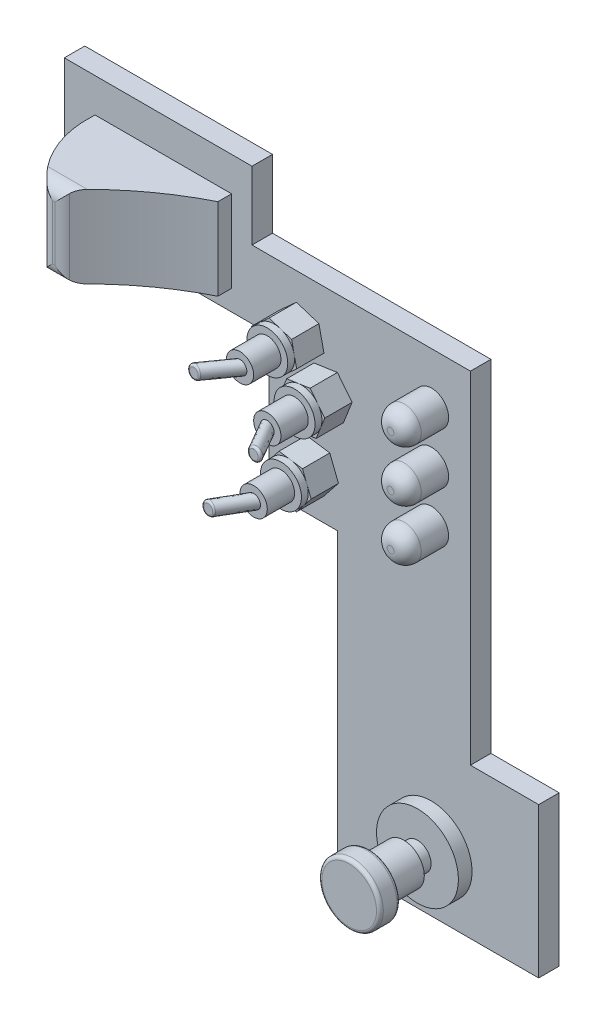
SolidWorks part; units mm, degrees
ref_plane "Front Plane" through (0, 0, 0) normal (0, 0, 1) x (1, 0, 0)
ref_plane "Top Plane" through (0, 0, 0) normal (0, 1, 0) x (1, 0, 0)
ref_plane "Right Plane" through (0, 0, 0) normal (1, 0, 0) x (0, 0, -1)
sketch "Sketch1" plane through (0, 0, 0) normal (0, 0, 1) x (1, 0, 0)
  line L1 (0, 0) -> (76.5, 0)
  line L2 (0, 0) -> (0, 100)
  line L3 (0, 100) -> (76.5, 100)
  line L4 (76.5, 0) -> (76.5, 100)
  dimension "D1" = 100
  dimension "D2" = 76.5
extrude "Boss-Extrude1" add sketch "Sketch1" along normal blind 3
sketch "Sketch3" plane through (0, 0, 3) normal (0, 0, 1) x (1, 0, 0)
  line L0 (76.5, 100) -> (0, 100) construction
  line L1 (76.5, 0) -> (76.5, 100) construction
  circle A0 centre (60.8, 64.5) radius 2.5
  circle A1 centre (60.8, 57) radius 2.5
  circle A2 centre (60.8, 49.5) radius 2.5
  point P6 (0, 0)
  dimension "D1" = 5
  dimension "D2" = 15
  dimension "D3" = 7.5
  dimension "D4" = 35.5
  dimension "D5" = 15.7
extrude "Boss-Extrude2" add sketch "Sketch3" along normal blind 6
fillet "Fillet1" radius 2 3 edges at (63.3, 49.5, 9) (63.3, 57, 9) (63.3, 64.5, 9)
sketch "Sketch4" plane through (0, 0, 3) normal (0, 0, 1) x (1, 0, 0)
  line L1 (11.5, 77) -> (31.5, 77)
  line L2 (11.5, 77) -> (11.5, 65)
  line L3 (11.5, 65) -> (31.5, 65)
  line L4 (31.5, 77) -> (31.5, 65)
  line L5 (0, 100) -> (0, 0) construction
  line L6 (76.5, 100) -> (0, 100) construction
  point P6 (0, 0)
  dimension "D1" = 11.5
  dimension "D2" = 12
  dimension "D3" = 20
  dimension "D4" = 23
extrude "Boss-Extrude3" add sketch "Sketch4" along normal blind 12
sketch "Sketch5" plane through (0, 65, 0) normal (0, -1, 0) x (1, 0, 0)
  line L0 (11.5, 15) -> (11.5, 3) construction
  line L1 (11.5, 15) -> (31.5, 15) construction
  line L2 (31.5, 15) -> (31.5, 3) construction
  line L3 (11.5, 5) -> (11.5, 15)
  line L4 (11.5, 15) -> (16.5, 15)
  line L5 (31.5, 5) -> (31.5, 15)
  line L6 (31.5, 15) -> (18.5, 15)
  arc A0 (11.5, 5) -> (16.5, 15) centre (25.8805, 4.0597) cw
  arc A1 (18.5, 15) -> (31.5, 5) centre (50.8168, 43.5618) ccw
  dimension "D1" = 5
  dimension "D5" = 14.4112
  dimension "D6" = 43.1295
  dimension "D2" = 10
  dimension "D3" = 10
  dimension "D4" = 2
extrude "Cut-Extrude1" cut sketch "Sketch5" against normal through all
fillet "Fillet2" radius 2 4 edges at (17.5, 65, 15) (16.5, 71, 15) (17.5, 77, 15) (18.5, 71, 15)
sketch "Sketch6" plane through (0, 0, 3) normal (0, 0, 1) x (1, 0, 0)
  line L0 (76.5, 0) -> (76.5, 100) construction
  line L1 (0, 0) -> (76.5, 0) construction
  circle A0 centre (60.739, 8.6048) radius 6
  point P3 (0, 0)
  dimension "D1" = 12
  dimension "D2" = 15.761
  dimension "D3" = 8.6048
extrude "Boss-Extrude4" add sketch "Sketch6" along normal blind 2
sketch "Sketch7" plane through (0, 0, 5) normal (0, 0, 1) x (1, 0, 0)
  line L0 (76.5, 0) -> (76.5, 100) construction
  line L1 (0, 0) -> (76.5, 0) construction
  circle A0 centre (60.739, 8.6048) radius 2
  point P3 (0, 0)
  dimension "D1" = 4
  dimension "D3" = 8.6048
  dimension "D2" = 15.761
extrude "Boss-Extrude5" add sketch "Sketch7" along normal blind 2
sketch "Sketch8" plane through (0, 0, 7) normal (0, 0, 1) x (1, 0, 0)
  line L0 (76.5, 0) -> (76.5, 100) construction
  line L1 (0, 0) -> (76.5, 0) construction
  circle A0 centre (60.739, 8.6048) radius 3
  point P3 (0, 0)
  dimension "D1" = 6
  dimension "D3" = 8.6048
  dimension "D2" = 15.761
extrude "Boss-Extrude6" add sketch "Sketch8" along normal blind 5
sketch "Sketch9" plane through (0, 0, 12) normal (0, 0, 1) x (1, 0, 0)
  line L0 (76.5, 0) -> (76.5, 100) construction
  line L1 (0, 0) -> (76.5, 0) construction
  circle A0 centre (60.739, 8.6048) radius 4.5
  point P3 (0, 0)
  dimension "D1" = 9
  dimension "D3" = 8.6048
  dimension "D2" = 15.761
extrude "Boss-Extrude7" add sketch "Sketch9" along normal blind 3
fillet "Fillet3" radius 0.5 1 edges at (65.239, 8.6048, 12)
fillet "Fillet4" radius 0.5 1 edges at (65.239, 8.6048, 15)
sketch "Sketch10" plane through (0, 0, 3) normal (0, 0, 1) x (1, 0, 0)
  line L1 (45.0373, 63.5458) -> (44.3053, 66.9317)
  line L2 (44.3053, 66.9317) -> (41.007, 67.9907)
  line L3 (41.007, 67.9907) -> (38.4407, 65.6639)
  line L4 (38.4407, 65.6639) -> (39.1727, 62.278)
  line L5 (39.1727, 62.278) -> (42.471, 61.219)
  line L6 (42.471, 61.219) -> (45.0373, 63.5458)
  line L7 (47.8968, 56.1503) -> (49.1648, 59.374)
  line L8 (49.1648, 59.374) -> (47.007, 62.084)
  line L9 (47.007, 62.084) -> (43.5812, 61.5702)
  line L10 (43.5812, 61.5702) -> (42.3132, 58.3466)
  line L11 (42.3132, 58.3466) -> (44.471, 55.6366)
  line L12 (44.471, 55.6366) -> (47.8968, 56.1503)
  line L13 (47.1648, 48.0911) -> (45.8968, 51.3148)
  line L14 (45.8968, 51.3148) -> (42.471, 51.8285)
  line L15 (42.471, 51.8285) -> (40.3132, 49.1186)
  line L16 (40.3132, 49.1186) -> (41.5812, 45.8949)
  line L17 (41.5812, 45.8949) -> (45.007, 45.3812)
  line L18 (45.007, 45.3812) -> (47.1648, 48.0911)
  line L19 (76.5, 100) -> (0, 100) construction
  line L20 (0, 100) -> (0, 0) construction
  circle A0 centre (41.739, 64.6048) radius 3 construction
  circle A1 centre (45.739, 58.8603) radius 3 construction
  circle A2 centre (43.739, 48.6048) radius 3 construction
  point P19 (50.2967, 56.2738)
  point P28 (44.8161, 67.3949)
  point P29 (0, 0)
  point P30 (0, 0)
  point P31 (0, 0)
  point P36 (49.1755, 59.297)
  dimension "D2" = 5.7446
  dimension "D3" = 10.2554
  dimension "D4" = 2
  dimension "D5" = 4
  dimension "D6" = 35.3952
  dimension "D7" = 41.739
  dimension "D1" = 6
  dimension "D8" = 6
  dimension "D9" = 2
  dimension "D10" = 5.9068
extrude "Boss-Extrude8" add sketch "Sketch10" along normal blind 4
sketch "Sketch11" plane through (0, 0, 3) normal (0, 0, 1) x (1, 0, 0)
  line L0 (7, 82) -> (7, 62)
  line L1 (7, 62) -> (37, 62)
  line L2 (37, 62) -> (37, 42)
  line L3 (37, 42) -> (47, 42)
  line L4 (47, 42) -> (47, 0)
  line L5 (0, 0) -> (76.5, 0) construction
  line L6 (47, 0) -> (0, 0)
  line L7 (0, 0) -> (0, 100)
  line L8 (0, 100) -> (76.5, 100)
  line L9 (76.5, 100) -> (76.5, 22)
  line L10 (76.5, 0) -> (76.5, 100) construction
  line L11 (76.5, 22) -> (66.5, 22)
  line L12 (66.5, 22) -> (66.5, 72)
  line L13 (66.5, 72) -> (34.5, 72)
  line L14 (34.5, 72) -> (34.5, 82)
  line L15 (34.5, 82) -> (7, 82)
  point P3 (0, 0)
  dimension "D1" = 20
  dimension "D2" = 18
  dimension "D3" = 7
  dimension "D4" = 42
  dimension "D5" = 32
  dimension "D6" = 20
  dimension "D7" = 10
  dimension "D8" = 10
  dimension "D9" = 30
  dimension "D10" = 50
extrude "Cut-Extrude2" cut sketch "Sketch11" against normal through all
sketch "Sketch12" plane through (0, 0, 7) normal (0, 0, 1) x (1, 0, 0)
  line L0 (44.3053, 66.9317) -> (41.007, 67.9907) construction
  line L2 (42.471, 61.219) -> (45.0373, 63.5458) construction
  line L3 (45.007, 45.3812) -> (47.1648, 48.0911) construction
  line L4 (40.3132, 49.1186) -> (41.5812, 45.8949) construction
  line L5 (47.007, 62.084) -> (43.5812, 61.5702) construction
  line L7 (47.8968, 56.1503) -> (49.1648, 59.374) construction
  circle A0 centre (41.739, 64.6048) radius 3
  circle A1 centre (45.739, 58.8603) radius 3
  circle A2 centre (43.739, 48.6048) radius 3
  point P8 (41.6864, 64.6217)
  dimension "D1" = 6
extrude "Boss-Extrude9" add sketch "Sketch12" along normal blind 1
sketch "Sketch13" plane through (0, 0, 8) normal (0, 0, 1) x (1, 0, 0)
  circle A0 centre (41.739, 64.6048) radius 2
  circle A1 centre (45.739, 58.8603) radius 2
  circle A2 centre (43.739, 48.6048) radius 2
  dimension "D1" = 4
extrude "Boss-Extrude10" add sketch "Sketch13" along normal blind 4
ref_plane "Plane2" through (0, 48.6, 0) normal (0, -1, 0) x (-1, 0, 0)
sketch "Sketch14" plane through (0, 48.6, 0) normal (0, -1, 0) x (-1, 0, 0)
  line L0 (-43.739, -12) -> (-41.239, -16.3301)
  line L1 (-45.739, -12) -> (-41.739, -12) construction
  dimension "D1" = 5
  dimension "D2" = 60
sketch "Sketch15" plane through (0, 0, 12) normal (0, 0, 1) x (1, 0, 0)
  circle A0 centre (43.739, 48.6048) radius 1
  dimension "D1" = 2
sweep "Sweep1" add profiles "Sketch15" path "Sketch14"
fillet "Fillet5" radius 0.3 1 edges at (42.239, 48.6048, 16.3301)
ref_plane "Plane3" through (0, 58.86, 0) normal (0, 1, 0) x (1, 0, 0)
sketch "Sketch17" plane through (0, 58.86, 0) normal (0, 1, 0) x (1, 0, 0)
  line L0 (45.739, -12) -> (48.239, -16.3301)
  line L1 (43.739, -12) -> (47.739, -12) construction
  dimension "D1" = 5
  dimension "D2" = 60
sketch "Sketch18" plane through (0, 0, 12) normal (0, 0, 1) x (1, 0, 0)
  circle A0 centre (45.739, 58.8603) radius 1
  dimension "D1" = 2
sweep "Sweep2" add profiles "Sketch18" path "Sketch17"
fillet "Fillet6" radius 0.3 1 edges at (49.239, 58.8603, 16.3301)
ref_plane "Plane4" through (0, 64.6, 0) normal (0, 1, 0) x (1, 0, 0)
sketch "Sketch19" plane through (0, 64.6, 0) normal (0, 1, 0) x (1, 0, 0)
  line L0 (41.739, -12) -> (38.8418, -16.0751)
  line L1 (39.739, -12) -> (43.739, -12) construction
  dimension "D1" = 5
sketch "Sketch20" plane through (0, 0, 12) normal (0, 0, 1) x (1, 0, 0)
  circle A0 centre (41.739, 64.6) radius 1
  dimension "D1" = 2
sweep "Sweep3" add profiles "Sketch20" path "Sketch19"
fillet "Fillet7" radius 0.3 1 edges at (39.8418, 64.6, 16.0751)
